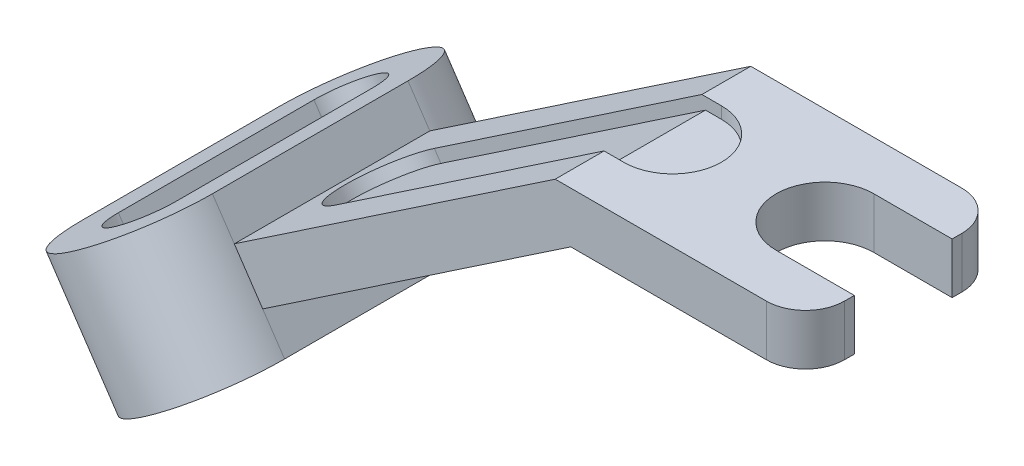
SolidWorks part; units mm, degrees
ref_plane "정면" through (0, 0, 0) normal (0, 0, 1) x (1, 0, 0)
ref_plane "윗면" through (0, 0, 0) normal (0, 1, 0) x (1, 0, 0)
ref_plane "우측면" through (0, 0, 0) normal (1, 0, 0) x (0, 0, -1)
sketch "Sketch1" plane through (0, 0, 0) normal (0, 0, 1) x (1, 0, 0)
  line L0 (60, 0) -> (0, 0)
  line L1 (0, 0) -> (-95.3393, -64.3072)
  line L2 (60, 13) -> (-3.9745, 13)
  line L3 (-3.9745, 13) -> (-102.6088, -53.5297)
  line L4 (60, 0) -> (60, 13)
  line L5 (-95.3393, -64.3072) -> (-102.6088, -53.5297)
  dimension "D1" = 60
  dimension "D2" = 115
  dimension "D4" = 146
  dimension "D3" = 13
extrude "Boss-Extrude1" add sketch "Sketch1" along normal blind 50 contours L2 L3 L5 L1 L0 L4
ref_plane "Plane1" through (-3.6348, 5.3887, 0) normal (0.5592, -0.829, 0) x (-0.829, -0.5592, 0)
sketch "Sketch3" plane through (-3.6348, 5.3887, 0) normal (0.5592, -0.829, 0) x (-0.829, -0.5592, 0)
  line L0 (115, 0) -> (115, -50) construction
  line L1 (0, -50) -> (115, -50) construction
  line L2 (115, -50) -> (115, 0) construction
  line L3 (135, 0) -> (135, -50)
  line L4 (95, 0) -> (95, -50)
  line L5 (115, -50) -> (115, 0) construction
  line L6 (106, -50) -> (106, 0)
  line L7 (124, -50) -> (124, 0)
  arc A0 (135, 0) -> (95, 0) centre (115, 0) ccw
  arc A1 (95, -50) -> (135, -50) centre (115, -50) ccw
  arc A2 (106, -50) -> (124, -50) centre (115, -50) ccw
  arc A3 (124, 0) -> (106, 0) centre (115, 0) ccw
  point P7 (115, -25)
  point P12 (115, -25)
  point P19 (0, 0)
  dimension "D1" = 20
  dimension "D2" = 9
extrude "Boss-Extrude2" add sketch "Sketch3" along normal mid plane 33
extrude "Cut-Extrude1" cut sketch "Sketch3<2>" against normal mid plane 33 contours A3 L6 A2 L7
sketch "Sketch3<2>" plane through (-3.6348, 5.3887, 0) normal (0.5592, -0.829, 0) x (-0.829, -0.5592, 0) same geometry as "Sketch3"
sketch "Sketch5" plane through (0, 13, 0) normal (0, 1, 0) x (1, 0, 0)
  line L0 (60, -25) -> (40, -25) construction
  line L1 (60, -50) -> (60, 0) construction
  line L2 (60, -37.5) -> (40, -37.5)
  line L3 (60, -12.5) -> (40, -12.5)
  line L4 (-3.9745, -25) -> (1.0255, -25) construction
  line L5 (-3.9745, -50) -> (-3.9745, 0) construction
  line L6 (-3.9745, -12.5) -> (1.0255, -12.5)
  line L7 (-3.9745, -37.5) -> (1.0255, -37.5)
  arc A0 (60, -37.5) -> (60, -12.5) centre (60, -25) ccw
  arc A1 (40, -12.5) -> (40, -37.5) centre (40, -25) ccw
  arc A2 (-3.9745, -12.5) -> (-3.9745, -37.5) centre (-3.9745, -25) ccw
  arc A3 (1.0255, -37.5) -> (1.0255, -12.5) centre (1.0255, -25) ccw
  point P4 (50, -25)
  point P9 (-1.4745, -25)
  line M6 (60, -50) -> (60, 0)
  dimension "D2" = 12.5
  dimension "D4" = 12.5
  dimension "D1" = 20
  dimension "D3" = 5
extrude "Cut-Extrude3" cut sketch "Sketch5" against normal through all contours L3 A1 L2 M6 region at (44.9607, 13, 25)
extrude "Cut-Extrude4" cut sketch "Sketch5<3>" against normal blind 3
sketch "Sketch5<3>" plane through (0, 13, 0) normal (0, 1, 0) x (1, 0, 0) same geometry as "Sketch5"
sketch "Sketch6" plane through (-7.2695, 10.7775, 0) normal (-0.5592, 0.829, 0) x (0.829, 0.5592, 0)
  line L0 (-78.5255, -25) -> (3.9745, -25) construction
  line L1 (-78.5255, -12.5) -> (3.9745, -12.5)
  line L2 (-78.5255, -37.5) -> (3.9745, -37.5)
  line L3 (3.9745, -12.5) -> (3.9745, 0) construction
  line L4 (3.9745, -50) -> (3.9745, -37.5) construction
  arc A0 (-78.5255, -12.5) -> (-78.5255, -37.5) centre (-78.5255, -25) ccw
  arc A1 (3.9745, -37.5) -> (3.9745, -12.5) centre (3.9745, -25) ccw
  point P2 (-37.2755, -25)
  point P9 (0, 0)
  dimension "D2" = 12.5
  dimension "D1" = 82.5
extrude "Cut-Extrude5" cut sketch "Sketch6" against normal blind 3
fillet "Fillet1" radius 10 2 edges at (60, 6.5, 0) (60, 6.5, 50)
